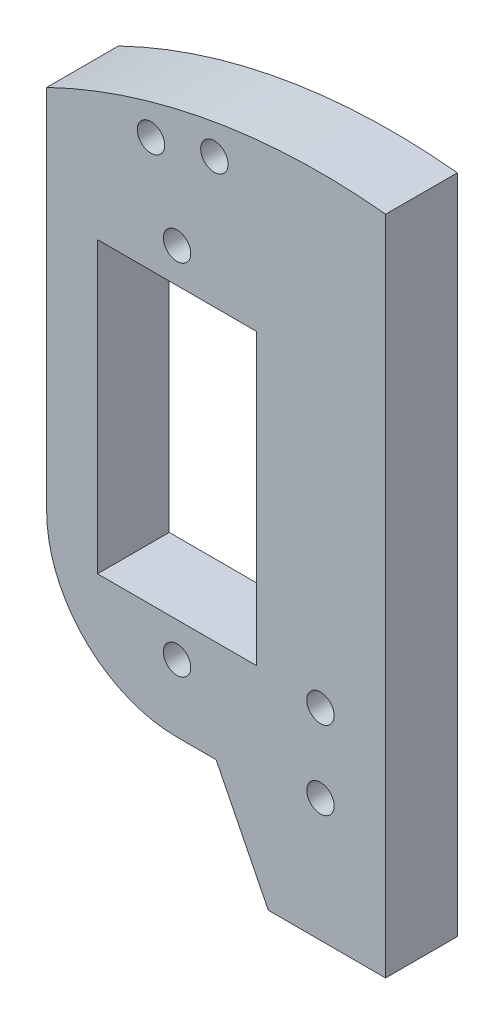
SolidWorks part; units mm, degrees
material "ﾁｰｸ材"
ref_plane "正面" through (0, 0, 0) normal (0, 0, 1) x (1, 0, 0)
ref_plane "平面" through (0, 0, 0) normal (0, 1, 0) x (1, 0, 0)
ref_plane "右側面" through (0, 0, 0) normal (1, 0, 0) x (0, 0, -1)
sketch "ｽｹｯﾁ1" plane through (0, 0, 0) normal (0, 0, 1) x (1, 0, 0)
  line L0 (-10, -18.9) -> (3, -18.9)
  line L1 (16, 26.1) -> (-10, 26.1)
  line L2 (16, 26.1) -> (16, -26.9)
  line L4 (-10, 26.1) -> (-10, -18.9)
  line L5 (3, -18.9) -> (7, -26.9)
  line L6 (7, -26.9) -> (16, -26.9)
  line L7 (6.1, 11.1) -> (-6.1, 11.1)
  line L8 (6.1, 11.1) -> (6.1, -11.1)
  line L9 (6.1, -11.1) -> (-6.1, -11.1)
  line L10 (-6.1, 11.1) -> (-6.1, -11.1)
  line L11 (6.1, 11.1) -> (-6.1, -11.1) construction
  line L12 (6.1, -11.1) -> (-6.1, 11.1) construction
  circle A0 centre (0, -13.75) radius 1.05
  circle A1 centre (0, 13.75) radius 1.05
  circle A2 centre (11, -17.45) radius 1.05
  circle A3 centre (11, -11.45) radius 1.05
  circle A4 centre (11, -23.9) radius 1.5 construction
  point P0 (0, 0)
  point P5 (0, 0)
  dimension "D3" = 2.1
  dimension "D10" = 2.1
  dimension "D12" = 3
  dimension "D1" = 22.2
  dimension "D2" = 12.2
  dimension "D4" = 2.65
  dimension "D5" = 2.65
  dimension "D6" = 18.9
  dimension "D7" = 10
  dimension "D8" = 16
  dimension "D9" = 3
  dimension "D11" = 6
  dimension "D13" = 12.45
  dimension "D14" = 5
  dimension "D15" = 26.1
  dimension "D16" = 9
  dimension "D17" = 13
  dimension "D18" = 26.9
extrude "ﾎﾞｽ - 押し出し1" add sketch "ｽｹｯﾁ1" along normal blind 5.5
sketch "ｽｹｯﾁ2" plane through (0, 0, 5.5) normal (0, 0, 1) x (1, 0, 0)
  line L0 (-10, 26.1) -> (-10, -18.9) construction
  line L1 (16, 26.1) -> (16, -26.9) construction
  line L2 (-10, 19.2625) -> (-10, 26.1)
  line L3 (-10, 26.1) -> (16, 26.1)
  line L4 (16, 26.1) -> (16, 23.8389)
  arc A0 (-10, 19.2625) -> (16, 23.8389) centre (11, -23.9) cw
  dimension "D1" = 48
extrude "ｶｯﾄ - 押し出し1" cut sketch "ｽｹｯﾁ2" against normal through all
fillet "ﾌｨﾚｯﾄ1" radius 10 1 edges at (-10, -18.9, 2.75)
sketch "ｽｹｯﾁ4" plane through (0, 0, 5.5) normal (0, 0, 1) x (1, 0, 0)
  line L0 (-2, 19.9428) -> (11, -23.9) construction
  line L1 (11, -23.9) -> (2.8642, 21.1) construction
  line L2 (-10, 26.1) -> (-10, -18.9) construction
  circle A0 centre (-2, 19.9428) radius 1.05
  circle A1 centre (2.8642, 21.1) radius 1.05
  dimension "D1" = 2.1
  dimension "D2" = 2.1
  dimension "D3" = 45
  dimension "D4" = 5
  dimension "D5" = 8
extrude "ｶｯﾄ - 押し出し2" cut sketch "ｽｹｯﾁ4" against normal through all
